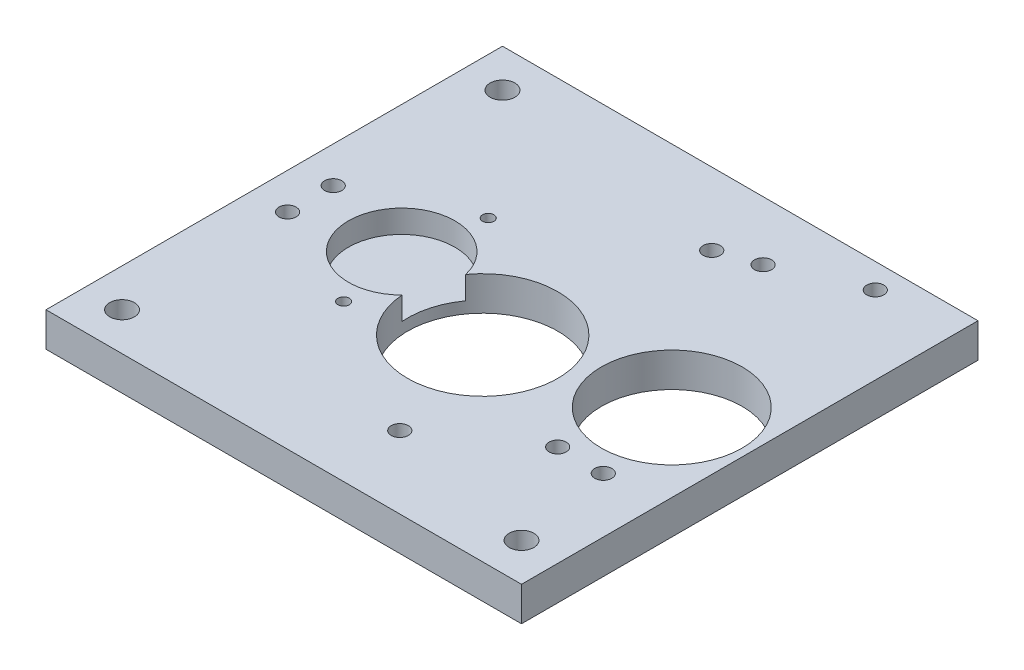
SolidWorks part; units mm, degrees
ref_plane "Front" through (0, 0, 0) normal (0, 0, 1) x (1, 0, 0)
ref_plane "Top" through (0, 0, 0) normal (0, 1, 0) x (1, 0, 0)
ref_plane "Right" through (0, 0, 0) normal (1, 0, 0) x (0, 0, -1)
sketch "Sketch1" plane through (0, 0, 0) normal (0, 1, 0) x (1, 0, 0)
  line L1 (0, 0) -> (125, 0)
  line L2 (0, 0) -> (0, 120)
  line L3 (0, 120) -> (125, 120)
  line L4 (125, 0) -> (125, 120)
  dimension "D1" = 125
  dimension "D2" = 120
extrude "Top_Base" add sketch "Sketch1" along normal blind 9
sketch "Fingers_Position" plane through (0, 9, 0) normal (0, 1, 0) x (1, 0, 0)
  line L0 (51, 79) -> (23.5, 79) construction
  line L1 (78.5, 63) -> (23.5, 63) construction
  line L2 (78.5, 63) -> (78.5, 95) construction
  line L3 (78.5, 95) -> (23.5, 95) construction
  line L4 (23.5, 63) -> (23.5, 95) construction
  line L5 (78.5, 25) -> (23.5, 25) construction
  line L6 (78.5, 25) -> (78.5, 57) construction
  line L7 (78.5, 57) -> (23.5, 57) construction
  line L8 (23.5, 25) -> (23.5, 57) construction
  line L9 (51, 95) -> (51, 63) construction
  line L10 (23.5, 41) -> (51, 41) construction
  line L11 (88.5, 109) -> (88.5, 54) construction
  line L12 (0, 120) -> (0, 0) construction
  line L13 (51, 57) -> (51, 25) construction
  line L14 (125, 60) -> (0, 60) construction
  line L15 (125, 0) -> (125, 120) construction
  line L16 (37.25, 41) -> (17.25, 41) construction
  line L17 (37.25, 41) -> (37.25, 21) construction
  line L18 (88.5, 54) -> (120.5, 54) construction
  line L19 (120.5, 54) -> (120.5, 109) construction
  line L20 (120.5, 109) -> (88.5, 109) construction
  line L21 (92.5, 69) -> (92.5, 33) construction
  line L22 (92.5, 33) -> (116.5, 33) construction
  line L23 (116.5, 33) -> (116.5, 69) construction
  line L24 (116.5, 69) -> (92.5, 69) construction
  line L25 (104.5, 109) -> (104.5, 54) construction
  line L26 (116.5, 51) -> (92.5, 51) construction
  circle A0 centre (37.25, 79) radius 20 construction
  circle A1 centre (37.25, 41) radius 20 construction
  circle A2 centre (37.25, 79) radius 20.5 construction
  circle A3 centre (37.25, 41) radius 20.5 construction
  circle A4 centre (37.25, 79) radius 19 construction
  circle A5 centre (37.25, 41) radius 19 construction
  circle A6 centre (104.5, 60) radius 9 construction
  circle A7 centre (104.5, 60) radius 17.75 construction
  point P44 (104.5, 69)
  dimension "D3" = 40
  dimension "D4" = 41
  dimension "D6" = 38
  dimension "D10" = 18
  dimension "D11" = 35.5
  dimension "D1" = 55
  dimension "D2" = 32
  dimension "D5" = 32
  dimension "D7" = 55
  dimension "D8" = 24
  dimension "D9" = 36
  dimension "D12" = 40
  dimension "D13" = 20.5
  dimension "D14" = 10
sketch "Intermediate_Gear_Position" plane through (0, 9, 0) normal (0, 1, 0) x (1, 0, 0)
  line L0 (24.5, 48) -> (24.5, 72) construction
  line L1 (24.5, 60) -> (42.5, 60) construction
  line L2 (42.5, 72) -> (42.5, 48) construction
  line L3 (9.5, 66) -> (9.5, 72) construction
  line L4 (42.5, 72) -> (6.5, 72) construction
  line L5 (92.5, 51) -> (116.5, 51) construction
  line L6 (6.5, 72) -> (6.5, 48) construction
  line L7 (42.5, 48) -> (6.5, 48) construction
  line L8 (104.5, 51) -> (104.5, 69) construction
  line L9 (125, 0) -> (125, 120) construction
  line L11 (88.5, 109) -> (120.5, 109) construction
  line L12 (120.5, 109) -> (120.5, 54) construction
  line L13 (120.5, 54) -> (88.5, 54) construction
  line L14 (88.5, 54) -> (88.5, 109) construction
  line L15 (92.5, 69) -> (92.5, 33) construction
  line L16 (92.5, 33) -> (116.5, 33) construction
  line L17 (116.5, 33) -> (116.5, 69) construction
  line L18 (116.5, 69) -> (92.5, 69) construction
  line L20 (104.5, 109) -> (104.5, 54) construction
  line L21 (9.5, 54) -> (9.5, 48) construction
  line L22 (125, 60) -> (0, 60) construction
  line L23 (78.5, 25) -> (78.5, 57) construction
  circle A0 centre (63.1461, 51.6485) radius 10 construction
  circle A3 centre (104.5, 60) radius 9 construction
  circle A4 centre (63.1461, 51.6485) radius 18 construction
  circle A6 centre (33.5, 60) radius 12.8 construction
  circle A8 centre (63.1461, 51.6485) radius 9 construction
  circle A9 centre (104.5, 60) radius 17.75 construction
  circle A10 centre (9.5, 54) radius 2 construction
  circle A11 centre (37.25, 41) radius 19 construction
  circle A12 centre (9.5, 66) radius 2 construction
  dimension "D3" = 20
  dimension "D4" = 18
  dimension "D5" = 6
  dimension "D2" = 36
  dimension "D6" = 25.6
  dimension "D17" = 35.5
  dimension "D18" = 4
  dimension "D19" = 6
  dimension "D22" = 4
  dimension "D7" = 24
  dimension "D8" = 36
  dimension "D9" = 32
  dimension "D10" = 55
  dimension "D11" = 24
  dimension "D12" = 36
  dimension "D13" = 40
  dimension "D14" = 20.5
  dimension "D15" = 36
  dimension "D16" = 3
  dimension "D20" = 360
  dimension "D21" = 3
sketch "Drive_Gear_Position" plane through (0, 9, 0) normal (0, 1, 0) x (1, 0, 0)
  line L21 (24.5, 48) -> (24.5, 72) construction
  circle A5 centre (33.5, 60) radius 14 construction
  circle A7 centre (33.5, 60) radius 13.5 construction
  dimension "D2" = 27
  dimension "D3" = 28
sketch "Sketch5" plane through (0, 9, 0) normal (0, 1, 0) x (1, 0, 0)
  circle A1 centre (33.5, 60) radius 14
  dimension "D1" = 28
extrude "Drive_Gear_Extrude_Cut" cut sketch "Sketch5" against normal blind 6 contours A1
sketch "Sketch8" plane through (0, 9, 0) normal (0, 1, 0) x (1, 0, 0)
  line L0 (104.5, 109) -> (104.5, 54) construction
  circle A0 centre (104.5, 60) radius 9 construction
  circle A1 centre (104.5, 60) radius 18.5
  dimension "D1" = 18
  dimension "D2" = 37
sketch "Sketch17" plane through (0, 9, 0) normal (0, 1, 0) x (1, 0, 0)
  circle A0 centre (63.1461, 51.6485) radius 19.75
  dimension "D1" = 39.5
extrude "Intermediate_Gear_Top_Part_Cut" cut sketch "Sketch17" against normal through all
extrude "Thumb_Extrude_Cut" cut sketch "Sketch8" against normal through all
sketch "Thumb_Mount_Holes" plane through (0, 9, 0) normal (0, 1, 0) x (1, 0, 0)
  line L5 (104.5, 109) -> (104.5, 113.5) construction
  line L6 (88.5, 109) -> (84, 109) construction
  line L11 (84, 109) -> (84, 104.5) construction
  line L13 (116.5, 36) -> (110.5, 36) construction
  line L15 (110.5, 36) -> (110.5, 33) construction
  line L31 (92.5, 33) -> (116.5, 33) construction
  line L32 (116.5, 33) -> (116.5, 69) construction
  line L33 (104.5, 51) -> (104.5, 33) construction
  line L34 (92.5, 51) -> (116.5, 51) construction
  circle A11 centre (104.5, 113.5) radius 2.25
  circle A12 centre (84, 104.5) radius 2.25
  circle A13 centre (110.5, 36) radius 2.25
  circle A14 centre (98.5, 36) radius 2.25
  dimension "D3" = 6
  dimension "D2" = 4.5
  dimension "D5" = 4.5
  dimension "D1" = 4.5
  dimension "D4" = 3
sketch "Connect_Holes_Position" plane through (0, 9, 0) normal (0, 1, 0) x (1, 0, 0)
  line L0 (0, 120) -> (10, 120) construction
  line L1 (125, 120) -> (0, 120) construction
  line L2 (10, 120) -> (10, 110) construction
  line L3 (125, 0) -> (115, 0) construction
  line L4 (0, 0) -> (125, 0) construction
  line L5 (115, 0) -> (115, 10) construction
  line L7 (0, 120) -> (0, 0) construction
  line L12 (0, 0) -> (0, 10) construction
  line L13 (0, 10) -> (10, 10) construction
  circle A0 centre (10, 110) radius 3.25
  circle A1 centre (115, 10) radius 3.25
  circle A4 centre (10, 10) radius 3.25
  dimension "D5" = 6.5
  dimension "D1" = 10
  dimension "D2" = 10
  dimension "D3" = 10
  dimension "D4" = 10
  dimension "D8" = 10
  dimension "D9" = 10
sketch "Fingers_Mount_Holes" plane through (0, 9, 0) normal (0, 1, 0) x (1, 0, 0)
  line L0 (78.5, 95) -> (78.5, 101) construction
  line L1 (78.5, 101) -> (74, 101) construction
  line L2 (125, 60) -> (0, 60) construction
  line L6 (6.5, 72) -> (6.5, 48) construction
  line L7 (24.5, 60) -> (6.5, 60) construction
  circle A0 centre (74, 101) radius 2.25
  circle A1 centre (74, 19) radius 2.25
  circle A2 centre (9.5, 54) radius 2.25
  circle A3 centre (9.5, 66) radius 2.25
  dimension "D3" = 4.5
  dimension "D4" = 4.5
  dimension "D1" = 6
  dimension "D2" = 4.5
sketch "Sketch26" plane through (0, 0, 0) normal (0, -1, 0) x (1, 0, 0)
  line L0 (37.25, -20.5) -> (37.25, -41) construction
  line L2 (0, -60) -> (125, -60) construction
  circle A0 centre (37.25, -41) radius 20.5 construction
  circle A1 centre (37.25, -41) radius 1.5
  circle A2 centre (37.25, -79) radius 1.5
  dimension "D2" = 3
extrude "String_Holes" cut sketch "Sketch26" against normal through all
extrude "Thumb_Mount_Holes_(M4)" cut sketch "Thumb_Mount_Holes" against normal through all
extrude "Fingers_Mount_Holes_(M4)" cut sketch "Fingers_Mount_Holes" against normal through all
extrude "Connect_Holes_(M6)" cut sketch "Connect_Holes_Position" against normal through all
sketch "Sketch27" plane through (0, 0, 0) normal (0, -1, 0) x (1, 0, 0)
  circle A0 centre (9.5, -66) radius 3.75
  circle A1 centre (9.5, -54) radius 3.75
  circle A2 centre (98.5, -36) radius 3.75
  circle A3 centre (110.5, -36) radius 3.75
  dimension "D1" = 7.5
extrude "XL320_Nut_(M4)" cut sketch "Sketch27" against normal blind 4
